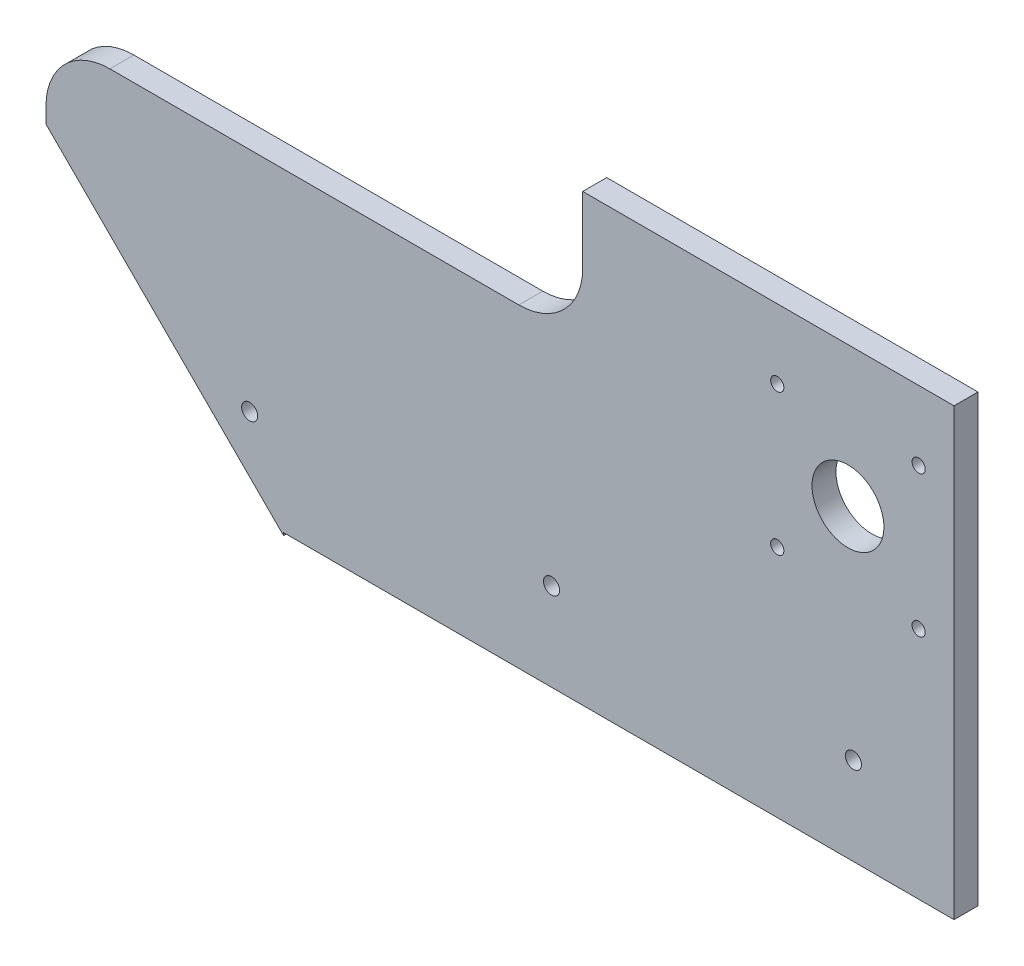
SolidWorks part; units mm, degrees
ref_plane "Front Plane" through (0, 0, 0) normal (0, 0, 1) x (1, 0, 0)
ref_plane "Top Plane" through (0, 0, 0) normal (0, 1, 0) x (1, 0, 0)
ref_plane "Right Plane" through (0, 0, 0) normal (1, 0, 0) x (0, 0, -1)
sketch "Sketch1" plane through (0, 0, 0) normal (0, 0, 1) x (1, 0, 0)
  line L0 (-138.2594, 48.9915) -> (32.2106, -121.4785)
  line L1 (32.2106, -121.4785) -> (222.7106, -121.4785)
  line L2 (-138.2594, 146.2068) -> (-138.2594, 48.9915)
  line L3 (-138.2594, 146.2068) -> (222.7106, 146.2068)
  line L4 (222.7106, -121.4785) -> (222.7106, 146.2068)
  circle A0 centre (180.538, 76.832) radius 14.2875
  circle A2 centre (180.538, 76.832) radius 69.85 construction
  circle A3 centre (180.538, 76.832) radius 318.7974 construction
  point P0 (0, 0)
  point P2 (180.538, 76.832)
  dimension "D4" = 198.3105
  dimension "D1" = 45
  dimension "D2" = 267.6854
  dimension "D5" = 245.11
extrude "Boss-Extrude1" add sketch "Sketch1" along normal blind 9.525
sketch "Sketch2" plane through (0, 0, 9.525) normal (0, 0, 1) x (1, 0, 0)
  line L0 (32.2106, -121.4785) -> (222.7106, -121.4785) construction
  line L1 (241.7606, -121.4785) -> (-43.8123, -121.4785)
  line L2 (241.7606, -121.4785) -> (241.7606, -44.3895)
  line L3 (241.7606, -44.3895) -> (-43.8123, -44.3895)
  line L4 (-43.8123, -121.4785) -> (-43.8123, -44.3895)
extrude "Cut-Extrude1" cut sketch "Sketch2" against normal through all contours L3 L4 L1 L2
sketch "Sketch4" plane through (0, 0, 9.525) normal (0, 0, 1) x (1, 0, 0)
  line L1 (-138.2594, 146.2068) -> (-138.2594, 48.9915) construction
  line L3 (-138.2594, 146.2068) -> (75.1006, 146.2068)
  line L4 (-138.2594, 146.2068) -> (-138.2594, 80.7415)
  line L5 (-138.2594, 80.7415) -> (75.1006, 80.7415)
  line L6 (75.1006, 146.2068) -> (75.1006, 80.7415)
extrude "Cut-Extrude2" cut sketch "Sketch4" against normal through all contours L5 L6 L3 L4
fillet "Fillet2" radius 25.4 2 edges at (-138.2594, 80.7415, 4.7625) (75.1006, 80.7415, 4.7625)
sketch "Sketch16" plane through (222.7106, 0, 0) normal (1, 0, 0) x (0, 0, -1)
  line L0 (0, -44.3895) -> (0, 146.2068) construction
  line L1 (-9.525, 146.2068) -> (0, 146.2068)
  line L2 (-9.525, 146.2068) -> (-9.525, 145.2215)
  line L3 (-9.525, 145.2215) -> (0, 145.2215)
  line L4 (0, 146.2068) -> (0, 145.2215)
extrude "Cut-Extrude3" cut sketch "Sketch16" against normal through all
sketch "Sketch17" plane through (0, 0, 0) normal (0, 0, -1) x (-1, 0, 0)
  line L0 (-222.7106, -44.3895) -> (-222.7106, 145.2215) construction
  line L1 (-75.1006, 145.2215) -> (-222.7106, 145.2215)
  line L2 (-75.1006, 145.2215) -> (-75.1006, 132.5215)
  line L3 (-75.1006, 132.5215) -> (-222.7106, 132.5215)
  line L4 (-222.7106, 145.2215) -> (-222.7106, 132.5215)
  dimension "D1" = 12.7
extrude "Cut-Extrude4" cut sketch "Sketch17" against normal through all
hole_wizard "Tap Drill for M6x0.75 Tap1" positions "Sketch19" profile "Sketch18" hole size "M6x0.75" standard "Lanco STD" end condition through all
sketch "Sketch19" plane through (0, 0, 9.525) normal (0, 0, 1) x (1, 0, 0)
  point P0 (208.638, 104.932)
  point P3 (152.438, 104.932)
  point P6 (152.438, 48.732)
  point P9 (208.638, 48.732)
sketch "Sketch18" plane through (208.638, 104.932, 9.525) normal (1, 0, 0) x (0, -1, 0)
  line L0 (0, 0) -> (0, 9.525)
  line L1 (0, 9.525) -> (2.625, 9.525)
  line L2 (2.625, 9.525) -> (2.625, 0)
  line L5 (2.625, 0) -> (0, 0)
  line L11 (0, -6.35) -> (0, 107.95) construction
  dimension "Thru Hole Dia." = 5.25
  dimension "Thru Hole Depth" = 9.525
hole_wizard "Ø6.4 (6.4) Diameter Hole1" positions "Sketch21" profile "Sketch20" hole size "Ø6.4" standard "ANSI Metric" end condition through all
sketch "Sketch21" plane through (0, 0, 9.525) normal (0, 0, 1) x (1, 0, 0)
  point P0 (-57.2894, -9.4645)
  point P2 (62.7106, -9.4645)
  point P4 (182.7106, -9.4645)
sketch "Sketch20" plane through (-57.2894, -9.4645, 9.525) normal (1, 0, 0) x (0, -1, 0)
  line L0 (0, 0) -> (0, 9.525)
  line L1 (0, 9.525) -> (3.2, 9.525)
  line L2 (3.2, 9.525) -> (3.2, 0)
  line L5 (3.2, 0) -> (0, 0)
  line L11 (0, -6.35) -> (0, 107.95) construction
  dimension "Thru Hole Dia." = 6.4
  dimension "Thru Hole Depth" = 9.525
